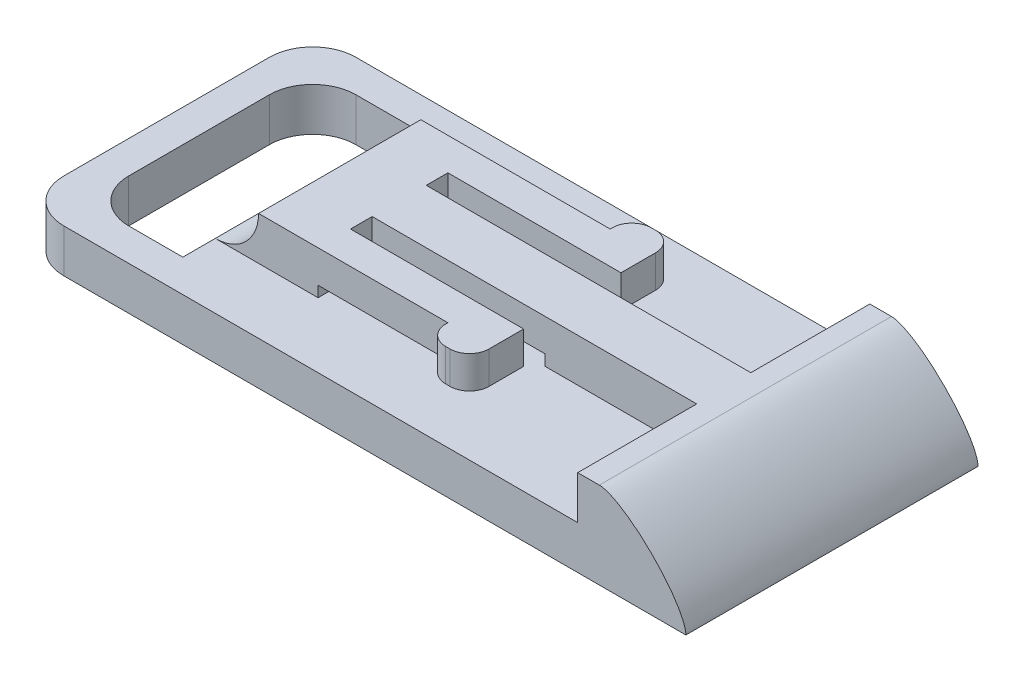
SolidWorks part; units mm, degrees
ref_plane "Front Plane" through (0, 0, 0) normal (0, 0, 1) x (1, 0, 0)
ref_plane "Top Plane" through (0, 0, 0) normal (0, 1, 0) x (1, 0, 0)
ref_plane "Right Plane" through (0, 0, 0) normal (1, 0, 0) x (0, 0, -1)
sketch "Sketch1" plane through (0, 0, 0) normal (0, 1, 0) x (1, 0, 0)
  line L1 (0, 0) -> (22.75, 0)
  line L2 (0, 0) -> (0, 13.5)
  line L3 (0, 13.5) -> (22.75, 13.5)
  line L4 (22.75, 0) -> (22.75, 13.5)
  dimension "D1" = 13.5
  dimension "D2" = 22.75
extrude "Boss-Extrude1" add sketch "Sketch1" along normal blind 4
fillet "Fillet1" radius 4 1 edges at (22.75, 4, -6.75) conic radius 10
sketch "Sketch2" plane through (0, 4, 0) normal (0, 1, 0) x (1, 0, 0)
  line L0 (0, 6.75) -> (22.75, 6.75) construction
  line L1 (0, 13.5) -> (0, 0) construction
  line L2 (22.75, 0) -> (22.75, 13.5) construction
  line L3 (17.75, 0) -> (17.75, 5.5)
  line L4 (0, 0) -> (18.75, 0) construction
  line L5 (17.75, 5.5) -> (2.75, 5.5)
  line L6 (2.75, 5.5) -> (2.75, 4.5)
  line L7 (2.75, 4.5) -> (10.75, 4.5)
  line L8 (10.75, 4.5) -> (10.75, 2.9)
  line L9 (9.85, 2) -> (9.65, 2)
  line L10 (8.75, 2.9) -> (8.75, 3)
  line L11 (8.75, 3) -> (0, 3)
  line L13 (0, 0) -> (17.75, 0)
  line L14 (0, 3) -> (0, 0)
  line L15 (0, 10.5) -> (0, 13.5)
  line L16 (0, 13.5) -> (17.75, 13.5)
  line L17 (8.75, 10.5) -> (0, 10.5)
  line L18 (8.75, 10.6) -> (8.75, 10.5)
  line L19 (9.85, 11.5) -> (9.65, 11.5)
  line L20 (10.75, 9) -> (10.75, 10.6)
  line L21 (2.75, 9) -> (10.75, 9)
  line L22 (2.75, 8) -> (2.75, 9)
  line L23 (17.75, 8) -> (2.75, 8)
  line L24 (17.75, 13.5) -> (17.75, 8)
  arc A0 (9.65, 2) -> (8.75, 2.9) centre (9.65, 2.9) cw
  arc A1 (10.75, 2.9) -> (9.85, 2) centre (9.85, 2.9) cw
  arc A2 (10.75, 10.6) -> (9.85, 11.5) centre (9.85, 10.6) ccw
  arc A3 (9.65, 11.5) -> (8.75, 10.6) centre (9.65, 10.6) ccw
  point P20 (8.75, 2)
  point P23 (10.75, 2)
  point P24 (10.75, 3.7)
  point P39 (10.75, 11.5)
  point P40 (8.75, 11.5)
  dimension "D9" = 0.9
  dimension "D1" = 5
  dimension "D2" = 1
  dimension "D3" = 1
  dimension "D4" = 7
  dimension "D5" = 1.5
  dimension "D6" = 3
  dimension "D7" = 2
  dimension "D8" = 8
extrude "Cut-Extrude1" cut sketch "Sketch2" against normal offset from surface (2 mm away) 2 up to face at (11.375, 0, -5.0625)
sketch "Sketch5" plane through (0, 0, -8) normal (0, 0, -1) x (-1, 0, 0)
  line L0 (-10.75, 2) -> (-10.75, 4) construction
  line L1 (-2.75, 2) -> (-10.75, 2)
  line L2 (-2.75, 2) -> (-2.75, 2.5)
  line L3 (-2.75, 2.5) -> (-10.75, 2.5)
  line L4 (-10.75, 2) -> (-10.75, 2.5)
  dimension "D1" = 0.5
extrude "Cut-Extrude2" cut sketch "Sketch5" against normal through all and the other way through all
sketch "Sketch4" plane through (0, 0, 0) normal (-1, 0, 0) x (0, 0, 1)
  line L1 (-13.5, 2) -> (0, 2)
  line L2 (-13.5, 2) -> (-13.5, 0)
  line L3 (-13.5, 0) -> (0, 0)
  line L4 (0, 2) -> (0, 0)
extrude "Boss-Extrude2" add sketch "Sketch4" along normal blind 8
sketch "Sketch6" plane through (0, 2, 0) normal (0, 1, 0) x (1, 0, 0)
  line L0 (-8, 0) -> (-8, 13.5) construction
  line L1 (-2, 12) -> (-6.5, 12)
  line L2 (-2, 12) -> (-2, 1.5)
  line L3 (-2, 1.5) -> (-6.5, 1.5)
  line L4 (-6.5, 12) -> (-6.5, 1.5)
  line L5 (17.75, 13.5) -> (-8, 13.5) construction
  line L6 (-8, 0) -> (17.75, 0) construction
  line L7 (0, 3) -> (0, 10.5) construction
  dimension "D1" = 1.5
  dimension "D2" = 1.5
  dimension "D3" = 1.5
  dimension "D4" = 2
extrude "Cut-Extrude3" cut sketch "Sketch6" against normal through all
fillet "Fillet3" radius 2 5 edges at (-8, 1, 0) (-8, 1, -13.5) (-6.5, 1, -12) (-6.5, 1, -1.5) (0, 2, -6.75)
